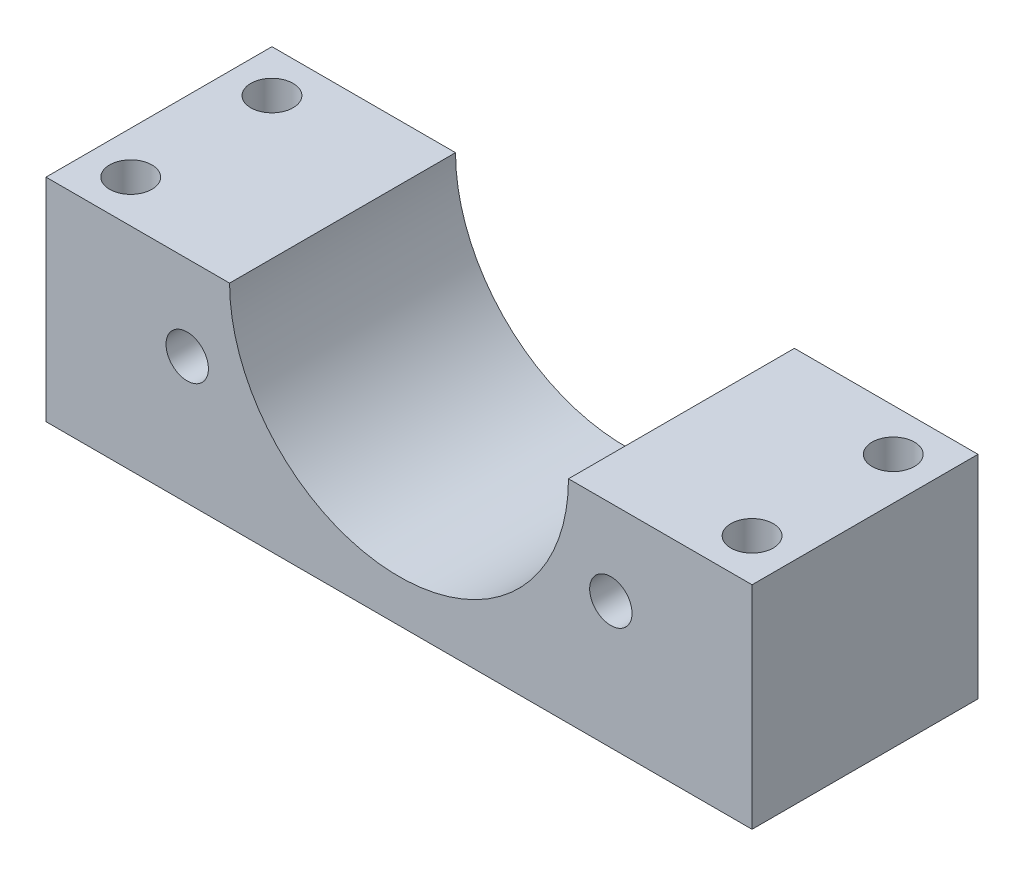
SolidWorks part; units mm, degrees
ref_plane "Front Plane" through (0, 0, 0) normal (0, 0, 1) x (1, 0, 0)
ref_plane "Top Plane" through (0, 0, 0) normal (0, 1, 0) x (1, 0, 0)
ref_plane "Right Plane" through (0, 0, 0) normal (1, 0, 0) x (0, 0, -1)
sketch "Sketch7" plane through (0, 0, 0) normal (0, 0, 1) x (1, 0, 0)
  line L0 (16.6062, 2.0295) -> (23.6062, 2.0295)
  line L1 (-14.3938, 2.0295) -> (-7.3938, 2.0295)
  line L3 (-14.3938, -12.9705) -> (27.6062, -12.9705)
  line L5 (-20.3938, -9.9705) -> (-20.3938, 2.0295)
  line L7 (-20.3938, -9.9705) -> (-20.3938, -12.9705)
  line L8 (-20.3938, -12.9705) -> (-14.3938, -12.9705)
  line L12 (27.6062, -12.9705) -> (29.6062, -12.9705)
  line L13 (29.6062, -9.9705) -> (29.6062, -12.9705)
  line L14 (-20.3938, 2.0295) -> (-14.3938, 2.0295)
  line L15 (23.6062, 2.0295) -> (29.6062, 2.0295)
  line L16 (29.6062, 2.0295) -> (29.6062, -9.9705)
  arc A0 (-7.3938, 2.0295) -> (16.6062, 2.0295) centre (4.6062, 2.0295) ccw
  circle A1 centre (-10.3938, -3.9705) radius 1.5
  circle A2 centre (19.6062, -3.9705) radius 1.5
  dimension "D3" = 15
  dimension "D4" = 24
  dimension "D11" = 3
  dimension "D12" = 6
  dimension "D15" = 3
  dimension "D1" = 15
  dimension "D2" = 38
  dimension "D5" = 50
  dimension "D6" = 3
  dimension "D9" = 3
  dimension "D14" = 6
  dimension "D16" = 0
extrude "Boss-Extrude11" add sketch "Sketch7" along normal blind 16
ref_plane "Plane2" through (0, 2.0295, 0) normal (0, 1, 0) x (1, 0, 0)
sketch3d "3DSketch1"
  line L0 (-20.3938, 2.0295, 16) -> (-20.3938, 2.0295, 0) construction
  line L1 (-7.3938, 2.0295, 0) -> (-20.3938, 2.0295, 0) construction
  line L2 (-7.3938, 2.0295, 16) -> (-20.3938, 2.0295, 16) construction
  line L3 (29.6062, 2.0295, 0) -> (16.6062, 2.0295, 0) construction
  line L4 (29.6062, 2.0295, 16) -> (29.6062, 2.0295, 0) construction
  line L5 (29.6062, 2.0295, 16) -> (16.6062, 2.0295, 16) construction
  circle A0 centre (-17.3938, 2.0295, 3) radius 1.5
  circle A1 centre (-17.3938, 2.0295, 13) radius 1.5
  circle A2 centre (26.6062, 2.0295, 3) radius 1.5
  circle A3 centre (26.6062, 2.0295, 13) radius 1.5
  point P2 (-17.3938, 3.5295, 3)
  point P9 (-17.3938, 3.5295, 13)
  point P15 (26.6062, 3.5295, 3)
  point P21 (26.6062, 3.5295, 13)
  dimension "D1" = 3
  dimension "D5" = 3
  dimension "D6" = 3
  dimension "D9" = 3
  dimension "D2" = 3
  dimension "D3" = 3
  dimension "D4" = 3
  dimension "D7" = 3
  dimension "D8" = 3
  dimension "D10" = 3
  dimension "D11" = 3
extrude "Cut-Extrude6" cut sketch "3DSketch1" along direction (0, -1, 0) on the side of the normal blind 16
